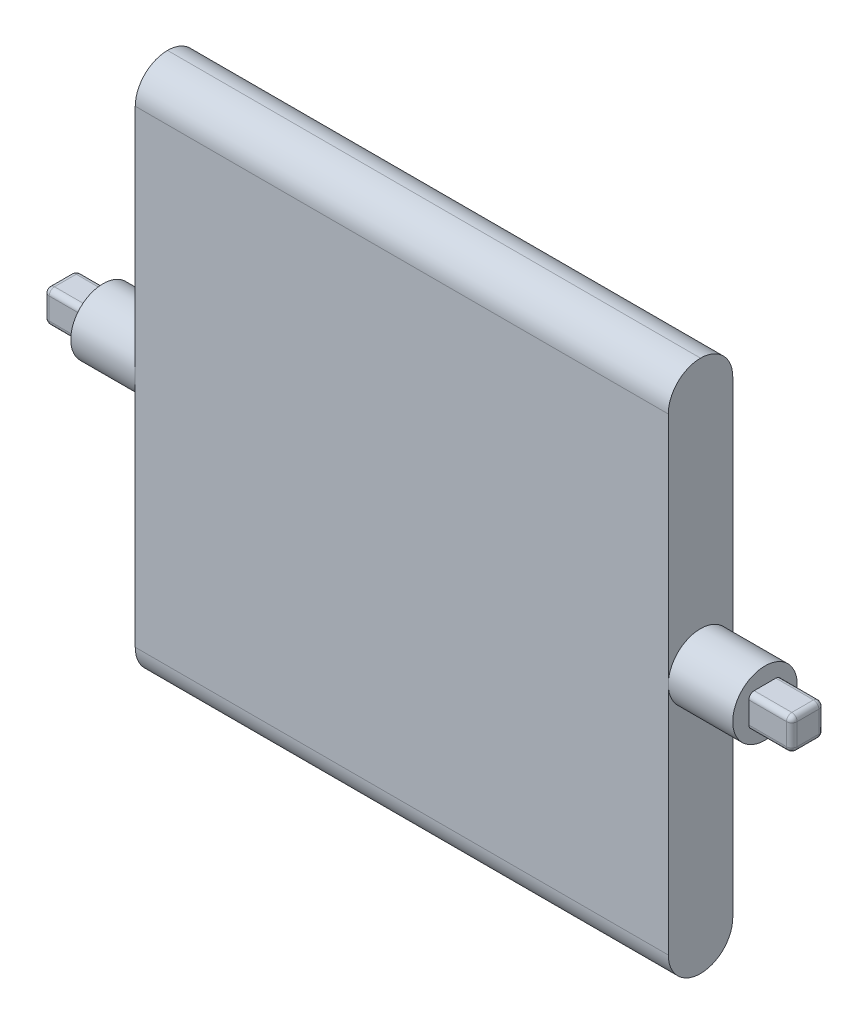
SolidWorks part; units mm, degrees
ref_plane "Front Plane" through (0, 0, 0) normal (0, 0, 1) x (1, 0, 0)
ref_plane "Top Plane" through (0, 0, 0) normal (0, 1, 0) x (1, 0, 0)
ref_plane "Right Plane" through (0, 0, 0) normal (1, 0, 0) x (0, 0, -1)
sketch "Sketch1" plane through (0, 0, 0) normal (0, 0, 1) x (1, 0, 0)
  line L1 (-39.37, -39.37) -> (39.37, -39.37)
  line L2 (-39.37, -39.37) -> (-39.37, 39.37)
  line L3 (-39.37, 39.37) -> (39.37, 39.37)
  line L4 (39.37, -39.37) -> (39.37, 39.37)
  line L5 (-39.37, -39.37) -> (39.37, 39.37) construction
  line L6 (-39.37, 39.37) -> (39.37, -39.37) construction
  point P0 (0, 0)
  dimension "D1" = 78.74
  dimension "D2" = 78.74
extrude "Boss-Extrude1" add sketch "Sketch1" along normal mid plane 9.525
sketch "Sketch2" plane through (39.37, 0, 0) normal (1, 0, 0) x (0, 0, -1)
  line L0 (0, 50.8) -> (0, 23.0111) construction
  line L2 (-4.7625, 0) -> (8.5114, 0) construction
  circle A0 centre (0, 0) radius 4.7625
  dimension "D1" = 9.525
extrude "Boss-Extrude2" add sketch "Sketch2" along normal blind 9.525
sketch "Sketch3" plane through (48.895, 0, 0) normal (1, 0, 0) x (0, 0, -1)
  line L5 (-2.3876, -2.3876) -> (2.3876, -2.3876)
  line L6 (-2.3876, -2.3876) -> (-2.3876, 2.3876)
  line L7 (-2.3876, 2.3876) -> (2.3876, 2.3876)
  line L8 (2.3876, -2.3876) -> (2.3876, 2.3876)
  line L9 (-2.3876, -2.3876) -> (2.3876, 2.3876) construction
  line L10 (-2.3876, 2.3876) -> (2.3876, -2.3876) construction
  point P0 (0, 0)
  dimension "D1" = 4.7752
  dimension "D2" = 4.7752
extrude "Boss-Extrude3" add sketch "Sketch3" along normal blind 6.35
mirror "Mirror1" about plane through (0, 0, 0) normal (1, 0, 0) of "Boss-Extrude3", "Boss-Extrude2"
fillet "Fillet2" radius 4.7625 4 edges at (0, -39.37, -4.7625) (0, -39.37, 4.7625) (0, 39.37, -4.7625) (0, 39.37, 4.7625)
fillet "Fillet3" radius 0.7874 4 edges at (-55.245, -2.3876, 0) (-55.245, 0, -2.3876) (-55.245, 2.3876, 0) (-55.245, 0, 2.3876)
fillet "Fillet4" radius 0.7874 4 edges at (55.245, 2.3876, 0) (55.245, 0, 2.3876) (55.245, -2.3876, 0) (55.245, 0, -2.3876)
fillet "Fillet5" radius 0.7874 16 edges at (-55.0144, -2.157, 2.157) (-55.0144, 2.157, 2.157) (-55.0144, -2.157, -2.157) (-55.0144, 2.157, -2.157) (55.0144, -2.157, 2.157) (55.0144, 2.157, 2.157) (55.0144, -2.157, -2.157) (55.0144, 2.157, -2.157) (-51.6763, -2.3876, 2.3876) (-51.6763, 2.3876, 2.3876) (-51.6763, -2.3876, -2.3876) (-51.6763, 2.3876, -2.3876) (51.6763, -2.3876, 2.3876) (51.6763, 2.3876, 2.3876) (51.6763, -2.3876, -2.3876) (51.6763, 2.3876, -2.3876)
